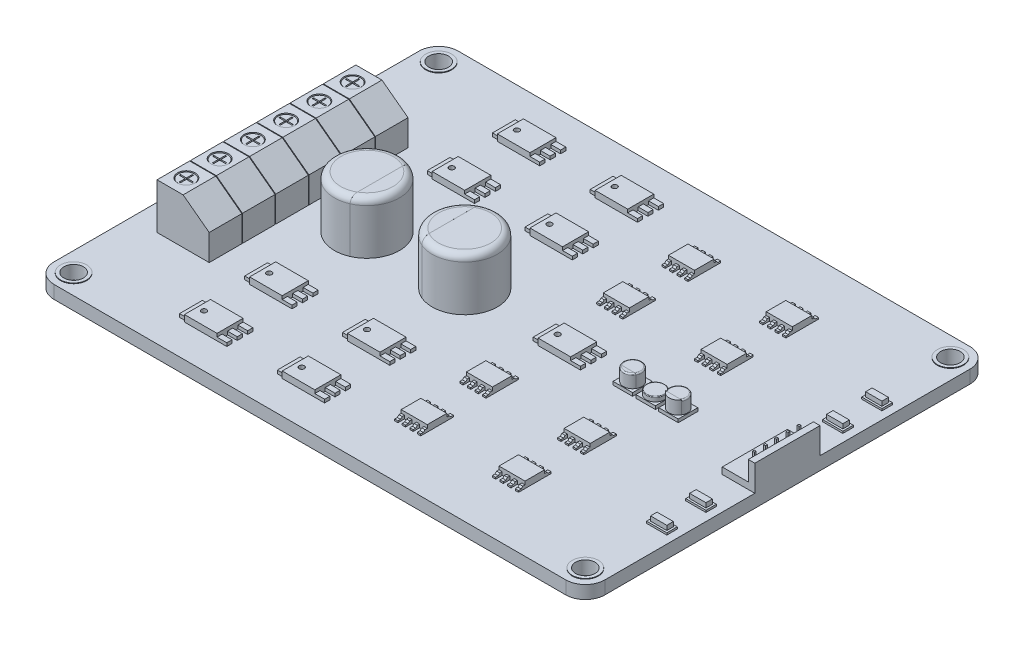
SolidWorks part; units mm, degrees
ref_plane "Front Plane" through (0, 0, 0) normal (0, 0, 1) x (1, 0, 0)
ref_plane "Top Plane" through (0, 0, 0) normal (0, 1, 0) x (1, 0, 0)
ref_plane "Right Plane" through (0, 0, 0) normal (1, 0, 0) x (0, 0, -1)
sketch "Sketch1" plane through (0, 0, 0) normal (0, 1, 0) x (1, 0, 0)
  line L1 (39.25, -31) -> (-39.25, -31)
  line L2 (42.25, -28) -> (42.25, 28)
  line L3 (39.25, 31) -> (-39.25, 31)
  line L4 (-42.25, -28) -> (-42.25, 28)
  line L5 (42.25, -31) -> (-42.25, 31) construction
  line L6 (42.25, 31) -> (-42.25, -31) construction
  circle A0 centre (-39.25, 28) radius 1.5
  circle A1 centre (39.25, 28) radius 1.5
  circle A2 centre (39.25, -28) radius 1.5
  circle A3 centre (-39.25, -28) radius 1.5
  arc A4 (-39.25, -31) -> (-42.25, -28) centre (-39.25, -28) cw
  arc A5 (39.25, -31) -> (42.25, -28) centre (39.25, -28) ccw
  arc A6 (-39.25, 31) -> (-42.25, 28) centre (-39.25, 28) ccw
  arc A7 (42.25, 28) -> (39.25, 31) centre (39.25, 28) ccw
  point P0 (0, 0)
  dimension "D3" = 3
  dimension "D8" = 3
  dimension "D1" = 84.5
  dimension "D2" = 62
  dimension "D4" = 56
  dimension "D5" = 28
  dimension "D6" = 78.5
  dimension "D7" = 39.25
extrude "Boss-Extrude1" add sketch "Sketch1" along normal blind 2
ref_plane "Plane1" through (0, 0, 1) normal (0, 0, 1) x (1, 0, 0)
sketch "Sketch8" plane through (0, 0, 1) normal (0, 0, 1) x (1, 0, 0)
  line L0 (-38.25, 2) -> (-38.25, 9)
  line L1 (-39.25, 2) -> (39.25, 2) construction
  line L2 (-38.25, 9) -> (-34.25, 9)
  line L3 (-34.25, 9) -> (-30.25, 6)
  line L4 (-30.25, 6) -> (-30.25, 2)
  line L5 (-30.25, 2) -> (-38.25, 2)
  line L6 (-42.25, 2) -> (-42.25, 0) construction
  dimension "D1" = 4
  dimension "D2" = 7
  dimension "D3" = 8
  dimension "D4" = 4
  dimension "D5" = 4
extrude "Boss-Extrude3" add sketch "Sketch8" along normal blind 5
sketch "Sketch9" plane through (0, 9, 0) normal (0, 1, 0) x (1, 0, 0)
  line L0 (-34.25, -1) -> (-38.25, -1) construction
  line L1 (-38.25, -6) -> (-38.25, -1) construction
  line L2 (-36.25, -3.5) -> (-36.25, -2.5)
  line L3 (-36.15, -4.5) -> (-36.15, -3.5)
  line L4 (-36.25, -4.5) -> (-36.25, -3.5)
  line L5 (-35.25, -3.5) -> (-37.25, -3.5)
  line L6 (-36.15, -3.5) -> (-36.15, -2.5)
  line L7 (-35.25, -3.4) -> (-37.25, -3.4)
  line L8 (-36.35, -4.5) -> (-36.35, -3.5)
  line L9 (-36.35, -3.5) -> (-36.35, -2.5)
  line L10 (-35.25, -3.6) -> (-37.25, -3.6)
  line L11 (-36.35, -2.5) -> (-36.15, -2.5)
  line L12 (-35.25, -3.4) -> (-35.25, -3.6)
  line L13 (-36.15, -4.5) -> (-36.35, -4.5)
  line L14 (-37.25, -3.6) -> (-37.25, -3.4)
  circle A0 centre (-36.25, -3.5) radius 1.25
  circle A1 centre (-36.25, -3.5) radius 1.35
  dimension "D1" = 2.5
  dimension "D2" = 2.5
  dimension "D3" = 2
  dimension "D5" = 1
  dimension "D6" = 1
  dimension "D7" = 1
  dimension "D8" = 1
  dimension "D4" = 0.1
  dimension "D9" = 0.1
  dimension "D10" = 0.1
extrude "Cut-Extrude2" cut sketch "Sketch9" against normal blind 2.5 contours A1 A0 region at (-37.5618, 9, 3.5)
extrude "Cut-Extrude4" cut sketch "Sketch9<4>" against normal blind 0.1 contours A0
sketch "Sketch9<4>" plane through (0, 9, 0) normal (0, 1, 0) x (1, 0, 0) same geometry as "Sketch9"
extrude "Cut-Extrude3" cut sketch "Sketch9<3>" against normal blind 0.5 contours L11 L2 L7 L6 | L11 L9 L7 L2 | L13 L3 L10 L4 | L13 L4 L10 L8 | L7 L14 L10 L12 region at (-36.3, 9, 2.95) region at (-36.2, 9, 2.95) region at (-36.2, 9, 4.05) region at (-36.3, 9, 4.05)
sketch "Sketch9<3>" plane through (0, 9, 0) normal (0, 1, 0) x (1, 0, 0) same geometry as "Sketch9"
pattern_linear "LPattern1" count 3 spacing 5.1 along (0, 0, 1) of "Boss-Extrude3", "Cut-Extrude2", "Cut-Extrude4", "Cut-Extrude3"
pattern_linear "LPattern2" count 4 spacing 5.1 along (0, 0, -1) of "Boss-Extrude3", "Cut-Extrude3", "Cut-Extrude2", "Cut-Extrude4"
sketch "Sketch10" plane through (0, 2, 0) normal (0, 1, 0) x (1, 0, 0)
  circle A11 centre (-39.25, 28) radius 2
  circle A12 centre (-39.25, 28) radius 2
  circle A14 centre (39.25, 28) radius 2
  circle A15 centre (39.25, 28) radius 2
  circle A17 centre (39.25, -28) radius 2
  circle A18 centre (39.25, -28) radius 2
  circle A19 centre (-39.25, -28) radius 1.5
  circle A20 centre (-39.25, -28) radius 2
  circle A21 centre (-39.25, -28) radius 2
  circle A22 centre (-39.25, 28) radius 1.5
  circle A23 centre (39.25, 28) radius 1.5
  circle A24 centre (39.25, -28) radius 1.5
  dimension "D1" = 0.5
  dimension "D2" = 0.5
  dimension "D3" = 0.5
  dimension "D4" = 0.5
extrude "Boss-Extrude4" add sketch "Sketch10" along normal blind 0.1
sketch "Sketch11" plane through (0, 2, 0) normal (0, 1, 0) x (1, 0, 0)
  line L0 (-42.25, 28) -> (-42.25, -28) construction
  circle A0 centre (-22.25, 0) radius 5
  circle A1 centre (-7.25, 0) radius 5
  dimension "D1" = 10
  dimension "D2" = 10
  dimension "D3" = 15
  dimension "D4" = 20
extrude "Boss-Extrude5" add sketch "Sketch11" along normal blind 8
fillet "Fillet1" radius 1 2 edges at (-7.25, 10, 5) (-22.25, 10, 5)
sketch "Sketch12" plane through (0, 2, 0) normal (0, 1, 0) x (1, 0, 0)
  line L0 (-42.25, 28) -> (-42.25, -28) construction
  line L1 (-24.25, -16) -> (-19.25, -16)
  line L2 (-24.25, -16) -> (-24.25, -12)
  line L3 (-24.25, -12) -> (-19.25, -12)
  line L4 (-19.25, -16) -> (-19.25, -12)
  line L5 (-39.25, -31) -> (39.25, -31) construction
  line L6 (-19.25, -16) -> (-17.75, -16)
  line L7 (-17.75, -16) -> (-17.75, -15.2)
  line L8 (-17.75, -15.2) -> (-19.25, -15.2)
  line L9 (-19.25, -14.401) -> (-17.75, -14.401)
  line L10 (-17.75, -14.401) -> (-17.75, -13.601)
  line L11 (-17.75, -13.601) -> (-19.25, -13.601)
  line L12 (-19.25, -12) -> (-17.75, -12)
  line L13 (-17.75, -12) -> (-17.75, -12.801)
  line L14 (-17.75, -12.801) -> (-19.25, -12.801)
  circle A0 centre (-23.25, -14) radius 0.4
  point P21 (-24.25, -14)
  dimension "D10" = 0.8
  dimension "D1" = 4
  dimension "D2" = 5
  dimension "D3" = 18
  dimension "D4" = 15
  dimension "D5" = 0.8
  dimension "D6" = 0.8
  dimension "D7" = 0.801
  dimension "D8" = 0.8
  dimension "D9" = 1.5
  dimension "D11" = 1
extrude "Boss-Extrude6" add sketch "Sketch12" along normal blind 1 contours L1 L4 L3 L2 region at (-21.7113, 2, 14)
extrude "Boss-Extrude7" add sketch "Sketch12<3>" along normal blind 0.5 contours L14 L13 L12 L4 | L10 L11 L4 L9 | L7 L8 L4 L6 region at (-18.5, 2, 15.6) region at (-18.5, 2, 12.4005) region at (-18.5, 2, 14.001)
sketch "Sketch12<3>" plane through (0, 2, 0) normal (0, 1, 0) x (1, 0, 0) same geometry as "Sketch12"
sketch "Sketch13" plane through (-24.25, 0, 0) normal (-1, 0, 0) x (0, 0, 1)
  line L0 (16, 2) -> (12, 2) construction
  line L1 (12.25, 2) -> (15.75, 2)
  line L2 (12.25, 2) -> (12.25, 2.5025)
  line L3 (12.25, 2.5025) -> (15.75, 2.5025)
  line L4 (15.75, 2) -> (15.75, 2.5025)
  line L5 (16, 3) -> (12, 3) construction
  point P6 (14, 2.5025)
  point P9 (14, 3)
  dimension "D1" = 0.5025
  dimension "D2" = 3.5
extrude "Boss-Extrude8" add sketch "Sketch13" along normal blind 1
pattern_linear "LPattern3" count 2 spacing 10 along (0, 0, 1) count 2 spacing 15 along (1, 0, 0) of "Boss-Extrude6", "Boss-Extrude7", "Boss-Extrude8"
sketch "Sketch14" plane through (0, 10, 0) normal (0, 1, 0) x (1, 0, 0)
  line L0 (-20.25, 4.5826) -> (-20.25, -4.5826)
  line L1 (-9.25, 4.5826) -> (-9.25, -4.5826)
  circle A0 centre (-22.25, 0) radius 5
  circle A1 centre (-7.25, 0) radius 5
  circle M4 centre (-22.25, 0) radius 4
  dimension "D1" = 10
  dimension "D2" = 3
  dimension "D3" = 3
extrude "Cut-Extrude5" cut sketch "Sketch14" against normal up to surface (8 mm away) contours L0 M4 | L0 A0 M4 | L1 A1 region at (-18.1474, 10, -2.6858) region at (-19.4299, 10, 0) region at (-10.4875, 10, 0) up to face at (-20.6875, 2, 24.0004)
sketch "Sketch15" plane through (0, 2, 0) normal (0, 1, 0) x (1, 0, 0)
  line L0 (-20.249, 4.5826) -> (-20.249, -4.5826)
  line L1 (-9.251, 4.5826) -> (-9.251, -4.5826)
  line L2 (-9.25, 4.5826) -> (-9.25, -4.5826) construction
  line L3 (-20.25, 4.5826) -> (-20.25, -4.5826) construction
  circle A0 centre (-22.25, 0) radius 5
  circle A1 centre (-7.25, 0) radius 5
  dimension "D1" = 10
  dimension "D2" = 0.001
  dimension "D3" = 0.001
extrude "Boss-Extrude9" add sketch "Sketch15" along normal up to surface (8 mm away) contours L0 A0 | L1 A1 region at (-19.012, 2, 0) region at (-10.488, 2, 0) up to face at (-6.25, 10, 0)
fillet "Fillet2" radius 1 2 edges at (-12.25, 10, 0) (-17.25, 10, 0)
sketch "Sketch16" plane through (0, 2, 0) normal (0, 1, 0) x (1, 0, 0)
  line L0 (6, -2) -> (11, -2)
  line L1 (6, -2) -> (6, 2)
  line L2 (6, 2) -> (11, 2)
  line L3 (11, -2) -> (11, 2)
  line L4 (11, 2) -> (12.5, 2)
  line L5 (12.5, 2) -> (12.5, 1.2)
  line L6 (12.5, 1.2) -> (11, 1.2)
  line L7 (11, 0.4) -> (12.5, 0.4)
  line L8 (12.5, 0.4) -> (12.5, -0.4)
  line L9 (12.5, -0.4) -> (11, -0.4)
  line L10 (11, -2) -> (12.5, -2)
  line L11 (12.5, -2) -> (12.5, -1.2)
  line L12 (12.5, -1.2) -> (11, -1.2)
  circle A0 centre (7, 0) radius 0.4
  point P5 (6, 0)
  dimension "D9" = 0.8
  dimension "D1" = 4
  dimension "D2" = 5
  dimension "D3" = 0.8
  dimension "D4" = 1.5
  dimension "D5" = 0.8
  dimension "D6" = 0.8
  dimension "D7" = 0.8
  dimension "D8" = 6
  dimension "D10" = 1
extrude "Boss-Extrude10" add sketch "Sketch16" along normal blind 1 contours L0 L3 L2 L1 region at (8.5387, 2, 0)
extrude "Boss-Extrude11" add sketch "Sketch16<3>" along normal blind 0.5 contours L6 L5 L4 L3 | L9 L8 L7 L3 | L11 L12 L3 L10 region at (11.75, 2, 1.6) region at (11.75, 2, -1.6) region at (11.75, 2, 0)
sketch "Sketch16<3>" plane through (0, 2, 0) normal (0, 1, 0) x (1, 0, 0) same geometry as "Sketch16"
sketch "Sketch17" plane through (6, 0, 0) normal (-1, 0, 0) x (0, 0, 1)
  line L0 (2, 2) -> (-2, 2) construction
  line L1 (-1.75, 2) -> (1.75, 2)
  line L2 (-1.75, 2) -> (-1.75, 2.5)
  line L3 (-1.75, 2.5) -> (1.75, 2.5)
  line L4 (1.75, 2) -> (1.75, 2.5)
  line L5 (2, 3) -> (-2, 3) construction
  point P6 (0, 2.5)
  point P9 (0, 3)
  dimension "D1" = 0.5
  dimension "D2" = 3.5
extrude "Boss-Extrude12" add sketch "Sketch17" along normal blind 1
sketch "Sketch18" plane through (0, 2, 0) normal (0, 1, 0) x (1, 0, 0)
  line L0 (5, -9) -> (5, -8)
  line L1 (5, -9) -> (9, -9)
  line L2 (5, -9) -> (5, -12)
  line L3 (5, -12) -> (9, -12)
  line L4 (9, -9) -> (9, -12)
  line L5 (5, -8) -> (5.5, -8)
  line L6 (5.5, -8) -> (5.5, -9)
  line L7 (6.1633, -9) -> (6.1633, -8)
  line L8 (6.1633, -8) -> (6.6633, -8)
  line L9 (6.6633, -8) -> (6.6633, -9)
  line L10 (7.3333, -9) -> (7.3333, -8)
  line L11 (7.3333, -8) -> (7.8333, -8)
  line L12 (7.8333, -8) -> (7.8333, -9)
  line L13 (8.5, -9) -> (8.5, -8)
  line L14 (8.5, -8) -> (9, -8)
  line L15 (9, -8) -> (9, -9)
  line L16 (9, -12) -> (9, -13)
  line L17 (9, -13) -> (8.5, -13)
  line L18 (8.5, -13) -> (8.5, -12)
  line L19 (7.8333, -12) -> (7.8333, -13)
  line L20 (7.8333, -13) -> (7.3333, -13)
  line L21 (7.3333, -13) -> (7.3333, -12)
  line L22 (6.6633, -12) -> (6.6633, -13)
  line L23 (6.6633, -13) -> (6.1633, -13)
  line L24 (6.1633, -13) -> (6.1633, -12)
  line L25 (5, -12) -> (5, -13)
  line L26 (5, -13) -> (5.5, -13)
  line L27 (5.5, -13) -> (5.5, -12)
  dimension "D1" = 3
  dimension "D2" = 4
  dimension "D3" = 0.5
  dimension "D4" = 0.5
  dimension "D5" = 0.6667
  dimension "D6" = 0.67
  dimension "D7" = 0.5
  dimension "D8" = 0.5
  dimension "D9" = 1
  dimension "D10" = 5
  dimension "D11" = 9
extrude "Boss-Extrude13" add sketch "Sketch18" along normal blind 1 contours L4 L1 L2 L3 region at (7, 2, 10.5)
extrude "Boss-Extrude14" add sketch "Sketch18<3>" along normal blind 0.5 contours L18 L17 L16 L3 | L21 L20 L19 L3 | L24 L23 L22 L3 | L26 L27 L3 L25 | L15 L14 L13 L1 | L12 L11 L10 L1 | L9 L8 L7 L1 | L6 L5 L0 L1 region at (5.25, 2, 8.5) region at (5.25, 2, 12.5) region at (6.4133, 2, 8.5) region at (6.4133, 2, 12.5) region at (7.5833, 2, 8.5) region at (7.5833, 2, 12.5) region at (8.75, 2, 8.5) region at (8.75, 2, 12.5)
sketch "Sketch18<3>" plane through (0, 2, 0) normal (0, 1, 0) x (1, 0, 0) same geometry as "Sketch18"
sketch "Sketch19" plane through (9, 0, 0) normal (1, 0, 0) x (0, 0, -1)
  line L0 (-28, 2) -> (28, 2) construction
  line L1 (-13, 2.5) -> (-12, 2.5)
  line L2 (-13, 2.5) -> (-13, 2)
  line L3 (-13, 2) -> (-12, 2)
  line L4 (-12, 2.5) -> (-12, 2)
  line L5 (-12, 2.5) -> (-12.3476, 2.5)
  line L6 (-12.3476, 2.5) -> (-12.5976, 2.25)
  line L7 (-12.5976, 2.25) -> (-13, 2.25)
  line L8 (-10.5, 3) -> (-10.5, 2) construction
  line L9 (-9, 3) -> (-12, 3) construction
  line L10 (-8, 2) -> (-13, 2) construction
  line L11 (-8.4024, 2.25) -> (-8, 2.25)
  line L12 (-8.6524, 2.5) -> (-8.4024, 2.25)
  line L13 (-8, 2) -> (-9, 2)
  line L14 (-9, 2.5) -> (-9, 2)
  line L15 (-8, 2.5) -> (-9, 2.5)
  line L16 (-8, 2.5) -> (-8, 2)
  line M9 (-8, 2) -> (-8, 2.5)
  line M10 (-8, 2.5) -> (-9, 2.5)
  line M15 (-13, 2.5) -> (-13, 2)
  dimension "D1" = 0.25
  dimension "D2" = 0.3476
extrude "Cut-Extrude6" cut sketch "Sketch19" against normal up to surface (4 mm away) contours L7 L6 L1 M15 | L12 L11 M10 M9 region at (9, 2.3849, 12.7314) region at (9, 2.3849, 8.2686) up to face at (5, 2.5, 10.5)
pattern_linear "LPattern4" count 2 spacing 10 along (0, 0, 1) count 2 spacing 15 along (1, 0, 0) of "Boss-Extrude13", "Cut-Extrude6", "Boss-Extrude14"
sketch "Sketch20" plane through (0, 2, 0) normal (0, 1, 0) x (1, 0, 0)
  line L1 (17, 1.5) -> (20, 1.5)
  line L2 (17, 1.5) -> (17, -1.5)
  line L3 (17, -1.5) -> (20, -1.5)
  line L4 (20, 1.5) -> (20, -1.5)
  point P4 (17, 0)
  dimension "D1" = 3
  dimension "D2" = 3
  dimension "D3" = 17
extrude "Boss-Extrude15" add sketch "Sketch20" along normal blind 0.5
pattern_linear "LPattern5" count 3 spacing 3.5 along (1, 0, 0) of "Boss-Extrude15"
sketch "Sketch21" plane through (0, 2.5, 0) normal (0, 1, 0) x (1, 0, 0)
  line L0 (20, 1.5) -> (17, 1.5) construction
  line L1 (17, 1.5) -> (17, -1.5) construction
  circle A0 centre (18.5, 0) radius 1.4
  point P6 (18.5, 1.5)
  point P10 (17, 0)
  dimension "D1" = 2.8
extrude "Boss-Extrude16" add sketch "Sketch21" along normal blind 2
sketch "Sketch22" plane through (0, 4.5, 0) normal (0, 1, 0) x (1, 0, 0)
  line L0 (17.2876, -0.7) -> (19.7124, -0.7)
  circle A0 centre (18.5, 0) radius 1.4
  circle M3 centre (18.5, 0) radius 1.4
  dimension "D1" = 2.8
  dimension "D2" = 0.7
extrude "Cut-Extrude7" cut sketch "Sketch22" against normal up to surface (2 mm away) contours L0 M3 region at (18.5, 4.5, 0.987) up to face at (18.5, 2.5, 1.4)
sketch "Sketch23" plane through (0, 4.5, 0) normal (0, 1, 0) x (1, 0, 0)
  line L0 (17.2881, -0.701) -> (19.7119, -0.701)
  line L1 (17.2876, -0.7) -> (19.7124, -0.7) construction
  circle A0 centre (18.5, 0) radius 1.4
  dimension "D1" = 2.8
  dimension "D2" = 0.001
extrude "Boss-Extrude17" add sketch "Sketch23" against normal up to surface (2 mm away) contours L0 A0 region at (18.5, 4.5, 0.9876) up to face at (18.5, 2.5, -0.35)
fillet "Fillet3" radius 0.2 1 edges at (18.5, 4.5, 1.4)
fillet "Fillet4" radius 0.2 1 edges at (18.5, 4.5, -1.4)
pattern_linear "LPattern6" count 2 spacing 7 along (1, 0, 0) of "Boss-Extrude16", "Boss-Extrude17", "Fillet4", "Cut-Extrude7"
sketch "Sketch24" plane through (0, 2.5, 0) normal (0, 1, 0) x (1, 0, 0)
  line L0 (23.5, 1.5) -> (20.5, 1.5) construction
  line L1 (20.5, 1.5) -> (20.5, -1.5) construction
  circle A0 centre (22, 0) radius 1.4
  point P5 (22, 1.5)
  point P9 (20.5, 0)
  dimension "D1" = 2.8
extrude "Boss-Extrude18" add sketch "Sketch24" along normal blind 0.7
fillet "Fillet5" radius 0.1 1 edges at (22, 3.2, 1.4)
sketch "Sketch25" plane through (0, 2, 0) normal (0, 1, 0) x (1, 0, 0)
  line L0 (42.25, -28) -> (42.25, 28) construction
  line L1 (37.25, 5) -> (42.25, 5)
  line L2 (37.25, 5) -> (37.25, -5)
  line L3 (37.25, -5) -> (42.25, -5)
  line L4 (42.25, 5) -> (42.25, -5)
  point P7 (37.25, 0)
  dimension "D1" = 10
  dimension "D2" = 5
extrude "Boss-Extrude19" add sketch "Sketch25" along normal blind 1
sketch "Sketch26" plane through (0, 3, 0) normal (0, 1, 0) x (1, 0, 0)
  line L0 (37.25, -5) -> (42.25, -5) construction
  line L1 (42.25, 5) -> (41.25, 5)
  line L2 (42.25, 5) -> (42.25, -5)
  line L3 (42.25, -5) -> (41.25, -5)
  line L4 (41.25, 5) -> (41.25, -5)
  dimension "D1" = 1
extrude "Boss-Extrude20" add sketch "Sketch26" along normal blind 3
sketch "Sketch27" plane through (0, 3, 0) normal (0, 1, 0) x (1, 0, 0)
  line L0 (41.25, 5) -> (41.25, -5) construction
  line L1 (40.45, 3.58) -> (40.75, 3.58)
  line L2 (40.45, 3.58) -> (40.45, 3.28)
  line L3 (40.45, 3.28) -> (40.75, 3.28)
  line L4 (40.75, 3.58) -> (40.75, 3.28)
  line L5 (41.25, 5) -> (37.25, 5) construction
  line L6 (40.45, 1.8633) -> (40.45, 1.5633)
  line L7 (40.45, 1.8633) -> (40.75, 1.8633)
  line L8 (40.75, 1.8633) -> (40.75, 1.5633)
  line L9 (40.45, 1.5633) -> (40.75, 1.5633)
  line L10 (40.45, 0.1467) -> (40.45, -0.1533)
  line L11 (40.45, 0.1467) -> (40.75, 0.1467)
  line L12 (40.75, 0.1467) -> (40.75, -0.1533)
  line L13 (40.45, -0.1533) -> (40.75, -0.1533)
  line L14 (40.45, -1.57) -> (40.45, -1.87)
  line L15 (40.45, -1.57) -> (40.75, -1.57)
  line L16 (40.75, -1.57) -> (40.75, -1.87)
  line L17 (40.45, -1.87) -> (40.75, -1.87)
  line L18 (40.45, -3.2867) -> (40.45, -3.5867)
  line L19 (40.45, -3.2867) -> (40.75, -3.2867)
  line L20 (40.75, -3.2867) -> (40.75, -3.5867)
  line L21 (40.45, -3.5867) -> (40.75, -3.5867)
  dimension "D1" = 0.3
  dimension "D2" = 0.5
  dimension "D3" = 1.42
  dimension "D5" = 1.4167
  dimension "D4" = 5
extrude "Boss-Extrude21" add sketch "Sketch27" along normal blind 3
sketch "Sketch28" plane through (0, 2, 0) normal (0, 1, 0) x (1, 0, 0)
  line L0 (37.25, -5) -> (41.25, -5) construction
  line L1 (38.25, -10) -> (40.75, -10)
  line L2 (38.25, -10) -> (38.25, -11)
  line L3 (38.25, -11) -> (40.75, -11)
  line L4 (40.75, -10) -> (40.75, -11)
  line L5 (42.25, -28) -> (42.25, -5) construction
  dimension "D1" = 5
  dimension "D2" = 1
  dimension "D3" = 2.5
  dimension "D4" = 1.5
extrude "Boss-Extrude22" add sketch "Sketch28" along normal blind 1
sketch "Sketch29" plane through (0, 2, 0) normal (0, 1, 0) x (1, 0, 0)
  line L8 (37.95, -9.7) -> (37.95, -11.3)
  line L9 (37.95, -11.3) -> (41.05, -11.3)
  line L10 (41.05, -11.3) -> (41.05, -9.7)
  line L11 (41.05, -9.7) -> (37.95, -9.7)
  line L12 (37.95, -9.7) -> (37.95, -11.3)
  line L13 (37.95, -11.3) -> (41.05, -11.3)
  line L14 (41.05, -11.3) -> (41.05, -9.7)
  line L15 (41.05, -9.7) -> (37.95, -9.7)
  dimension "D1" = 0.3
extrude "Boss-Extrude23" add sketch "Sketch29" along normal blind 0.3
pattern_linear "LPattern7" count 2 spacing 6 along (0, 0, 1) of "Boss-Extrude23", "Boss-Extrude22"
mirror "Mirror1" about plane through (0, 0, 0) normal (0, 0, 1) of "Boss-Extrude23", "Boss-Extrude22", "LPattern7", "LPattern3", "LPattern4"
